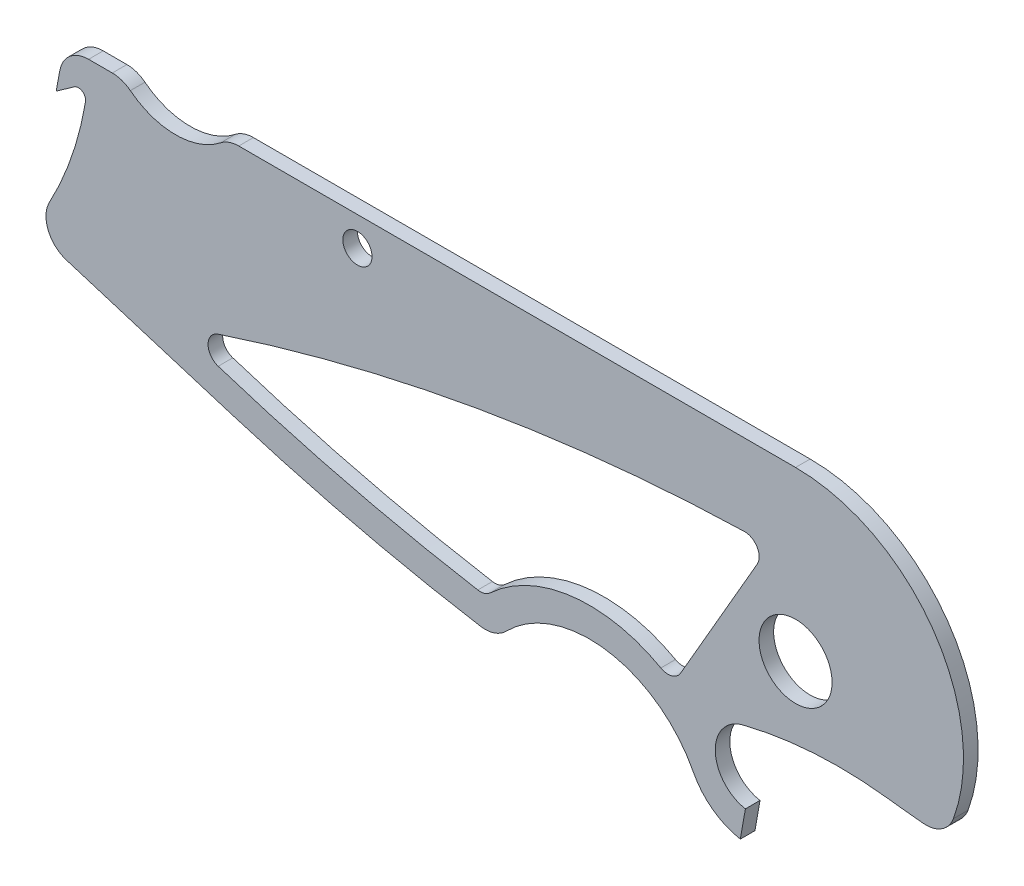
SolidWorks part; units mm, degrees
material "Obyčejná uhlíková ocel"
ref_plane "Přední rovina" through (0, 0, 0) normal (0, 0, 1) x (1, 0, 0)
ref_plane "Horní rovina" through (0, 0, 0) normal (0, 1, 0) x (1, 0, 0)
ref_plane "Pravá rovina" through (0, 0, 0) normal (1, 0, 0) x (0, 0, -1)
sketch "Skica15" plane through (0, 0, 0) normal (0, 0, 1) x (1, 0, 0)
  line L0 (0, 10) -> (0, -10)
  line L1 (0, 0) -> (-50, 0) construction
  line L2 (-1.7365, -9.8481) -> (1.7365, 9.8481)
  line L3 (0, 0) -> (49.2404, -8.6824) construction
  arc A0 (-50, 0) -> (0, 10) centre (0, -120) cw
  arc A1 (-50, 0) -> (0, -10) centre (0, 120) ccw
  arc A2 (1.7365, 9.8481) -> (49.2404, -8.6824) centre (-20.8378, -118.1769) cw
  arc A3 (-1.7365, -9.8481) -> (49.2404, -8.6824) centre (20.8378, 118.1769) ccw
  circle A4 centre (0, 0) radius 10
  dimension "D2" = 130
  dimension "D1" = 20
  dimension "D3" = 50
  dimension "D4" = 10
sketch "Skica1" plane through (0, 0, 0) normal (0, 0, 1) x (1, 0, 0)
  line L0 (0, 11.5) -> (-38.1264, 11.5)
  line L1 (-46.7866, 11.5) -> (-48.4086, 11.5)
  line L2 (0, 0) -> (-59.5409, 0) construction
  line L3 (-3, -8) -> (-3, -17.0212) construction
  line L4 (-3.4341, -10.462) -> (-3.7814, -12.4316)
  line L5 (-49.9157, -1.1721) -> (-38.4483, -4.7076)
  line L9 (0, 10) -> (0, -10) construction
  circle A0 centre (0, 0) radius 2.5
  arc A1 (10.8103, -3.9228) -> (0, 11.5) centre (0, 0) ccw
  arc A2 (8.735, -5.231) -> (6.1726, -4.9528) centre (20.8378, 118.1769) cw
  arc A3 (-3.6079, -5.575) -> (-3.4341, -10.462) centre (-3, -8) ccw
  arc A4 (-7, -10.0616) -> (-3.7814, -12.4316) centre (-3, -8) ccw
  arc A5 (-1.7365, -9.8481) -> (49.2404, -8.6824) centre (20.8378, 118.1769) ccw construction
  arc A6 (-50.3712, 9.8851) -> (-51.3262, 0.7691) centre (0, 0) ccw
  arc A7 (6.1726, -4.9528) -> (-3.6079, -5.575) centre (2.9721, -31.8245) ccw
  arc A8 (-7, -10.0616) -> (-19.8268, -8.1292) centre (-14.1111, -13.7265) ccw
  arc A9 (-51.3262, 0.7691) -> (-49.9157, -1.1721) centre (-49.3265, 0.7391) ccw
  arc A10 (-21.5866, -8.7023) -> (-38.4483, -4.7076) centre (0, 120) cw
  circle A11 centre (-50, 0) radius 1 construction
  arc A12 (-21.5866, -8.7023) -> (-19.8268, -8.1292) centre (-21.2557, -6.7298) ccw
  arc A13 (-50, 0) -> (0, -10) centre (0, 120) ccw construction
  arc A14 (8.735, -5.231) -> (10.8103, -3.9228) centre (8.9302, -3.2406) ccw
  arc A15 (-45.5495, 11.0714) -> (-39.3636, 11.0714) centre (-42.4565, 15) ccw
  arc A16 (-39.3636, 11.0714) -> (-38.1264, 11.5) centre (-38.1264, 9.5) cw
  arc A17 (-45.5495, 11.0714) -> (-46.7866, 11.5) centre (-46.7866, 9.5) ccw
  arc A18 (-50.3712, 9.8851) -> (-48.4086, 11.5) centre (-48.4086, 9.5) cw
  point P34 (-20.4784, -8.8832)
  point P36 (10.1726, -5.3636)
  point P47 (-46.0272, 11.5)
  point P50 (-50.0272, 11.5)
  dimension "D1" = 5
  dimension "D2" = 11.5
  dimension "D3" = 2
  dimension "D4" = 5
  dimension "D5" = 3
  dimension "D6" = 8
  dimension "D7" = 2
  dimension "D10" = 2
  dimension "D11" = 4
  dimension "D13" = 6
  dimension "D14" = 12
  dimension "D12" = 2
  dimension "D9" = 0.5
  dimension "D16" = 8
  dimension "D17" = 4
  dimension "D19" = 4
  dimension "D15" = 2
  dimension "D18" = 5
  dimension "D21" = 2
  dimension "D22" = 2
  dimension "D23" = 2
  dimension "D8" = 10
  dimension "D20" = 1.5
extrude "Přidat vysunutím1" add sketch "Skica1" along normal blind 1
ref_plane "Rovina1" through (0, 0, 2) normal (0, 0, 1) x (1, 0, 0)
sketch "Skica14" plane through (0, 0, 2) normal (0, 0, 1) x (1, 0, 0)
  line L0 (-7.8691, -4.6297) -> (-2.6262, 4.4512)
  line L1 (0, 0) -> (-50, 0) construction
  arc A0 (-39.5364, -2.2666) -> (-21.758, -6.6445) centre (0, 120) ccw
  arc A1 (-39.5426, -0.3656) -> (-3.5202, 5.9508) centre (0, -120) cw
  arc A2 (-38.4483, -4.7076) -> (-21.5866, -8.7023) centre (0, 120) ccw construction
  arc A4 (-39.5426, -0.3656) -> (-39.5364, -2.2666) centre (-39.2288, -1.3151) ccw
  arc A5 (-20.9089, -6.3924) -> (-21.758, -6.6445) centre (-21.5887, -5.659) cw
  arc A6 (-2.6262, 4.4512) -> (-3.5202, 5.9508) centre (-3.4923, 4.9512) ccw
  arc A7 (0, 10) -> (-50, 0) centre (0, -120) ccw construction
  arc A8 (-20.9089, -6.3924) -> (-9.2239, -5.0022) centre (-14.1111, -13.7265) cw
  arc A10 (-9.2239, -5.0022) -> (-7.8691, -4.6297) centre (-8.7351, -4.1297) ccw
  arc A13 (-7, -10.0616) -> (-19.8268, -8.1292) centre (-14.1111, -13.7265) ccw construction
  arc A14 (-38.4483, -4.7076) -> (-21.5866, -8.7023) centre (0, 120) ccw construction
  circle A15 centre (0, 0) radius 2.5 construction
  dimension "D2" = 2
  dimension "D3" = 2
  dimension "D4" = 2
  dimension "D5" = 4
  dimension "D6" = 2
  dimension "D1" = 60
extrude "Odebrat vysunutím13" cut sketch "Skica14" against normal through all and the other way through all
sketch "Skica13" plane through (0, 0, 0) normal (0, 0, 1) x (1, 0, 0)
  line L0 (-50.6234, 8.5) -> (-49.4017, 9.3704)
  line L1 (-50.6234, 8.5) -> (-50.1369, 11.3972) construction
  line L3 (0, 11.5) -> (-38.1264, 11.5) construction
  line L4 (-48.6185, 8.8804) -> (-49.8187, 1.7325) construction
  arc A1 (-49.4017, 9.3704) -> (-48.6185, 8.8804) centre (-49.1116, 8.9632) cw
  arc A2 (-50.3712, 9.8851) -> (-51.3262, 0.7691) centre (0, 0) ccw construction
  arc A3 (-51.3262, 0.7691) -> (-49.9157, -1.1721) centre (-49.3265, 0.7391) ccw construction
  arc A4 (-50.3712, 9.8851) -> (-51.3262, 0.7691) centre (0, 0) ccw construction
  arc A6 (-48.6185, 8.8804) -> (-51.0865, 1.6889) centre (-71.5477, 12.7303) cw
  arc A7 (-51.0865, 1.6889) -> (-51.3262, 0.7691) centre (-49.3265, 0.7391) ccw
  dimension "D3" = 1
  dimension "D5" = 45
  dimension "D1" = 45
  dimension "D2" = 1.5
  dimension "D4" = 3
extrude "Odebrat vysunutím12" cut sketch "Skica13" against normal through all and the other way through all flip side to cut
sketch "Skica16" plane through (0, 0, 0) normal (0, 0, 1) x (1, 0, 0)
  line L0 (0, 10) -> (0, -10) construction
  line L1 (0, 11.5) -> (-38.1264, 11.5) construction
  circle A0 centre (-30, 9.5) radius 1
  dimension "D1" = 2
  dimension "D2" = 30
  dimension "D3" = 2
extrude "Odebrat vysunutím15" cut sketch "Skica16" along normal through all
